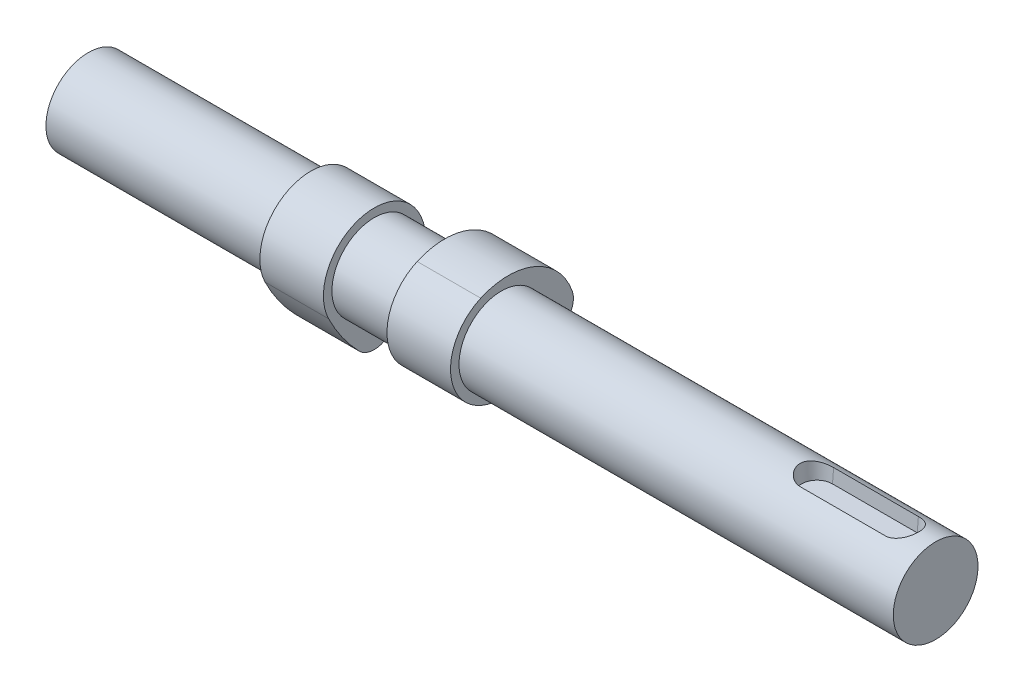
SolidWorks part; units mm, degrees
ref_plane "Front Plane" through (0, 0, 0) normal (0, 0, 1) x (1, 0, 0)
ref_plane "Top Plane" through (0, 0, 0) normal (0, 1, 0) x (1, 0, 0)
ref_plane "Right Plane" through (0, 0, 0) normal (1, 0, 0) x (0, 0, -1)
sketch "Sketch2" plane through (0, 0, 0) normal (1, 0, 0) x (0, 0, -1)
  circle A0 centre (0, 0) radius 10
  dimension "D1" = 20
extrude "Boss-Extrude1" add sketch "Sketch2" along normal blind 125 and the other way blind 75
sketch "Sketch3" plane through (0, 0, 0) normal (1, 0, 0) x (0, 0, -1)
  arc A0 (-4.8671, 10.9687) -> (5.3062, -10.7631) centre (0, 0) ccw
  arc A1 (-4.8671, 10.9687) -> (16.7127, 1.6619) centre (1.6224, -3.6562) cw
  arc A2 (5.3062, -10.7631) -> (15.4795, -3.5877) centre (-12.3812, 25.1139) ccw
  arc A3 (16.7127, 1.6619) -> (15.4795, -3.5877) centre (11.997, 0) cw
  dimension "D1" = 5
  dimension "D2" = 24
  dimension "D3" = 40
  dimension "D4" = 16
  dimension "D5" = 12.5
extrude "Boss-Extrude2" add sketch "Sketch3" along normal mid plane 15 from offset 15 separate body
mirror "Mirror1" about plane through (0, 0, 0) normal (1, 0, 0) of bodies 102
move or copy body "Body-Move/Copy1" bodies to move or copy 103 copy no rotation origin (0, 0, 0) rotation axis (-1, 0, 0) rotation angle 90 parameters "Angle Around Edge"=270
sketch "Sketch4" plane through (0, 0, 0) normal (0, 1, 0) x (1, 0, 0)
  line L0 (125, 0) -> (99.611, 0) construction
  line L1 (125, -10) -> (125, 10) construction
  line L2 (97, 0) -> (117, 0) construction
  line L3 (97, 4) -> (117, 4)
  line L4 (97, -4) -> (117, -4)
  arc A0 (97, 4) -> (97, -4) centre (97, 0) ccw
  arc A1 (117, -4) -> (117, 4) centre (117, 0) ccw
  point P7 (107, 0)
  dimension "D1" = 4
  dimension "D2" = 20
  dimension "D3" = 8
extrude "Cut-Extrude1" cut sketch "Sketch4" against normal blind 4 draft 5 from offset 10
